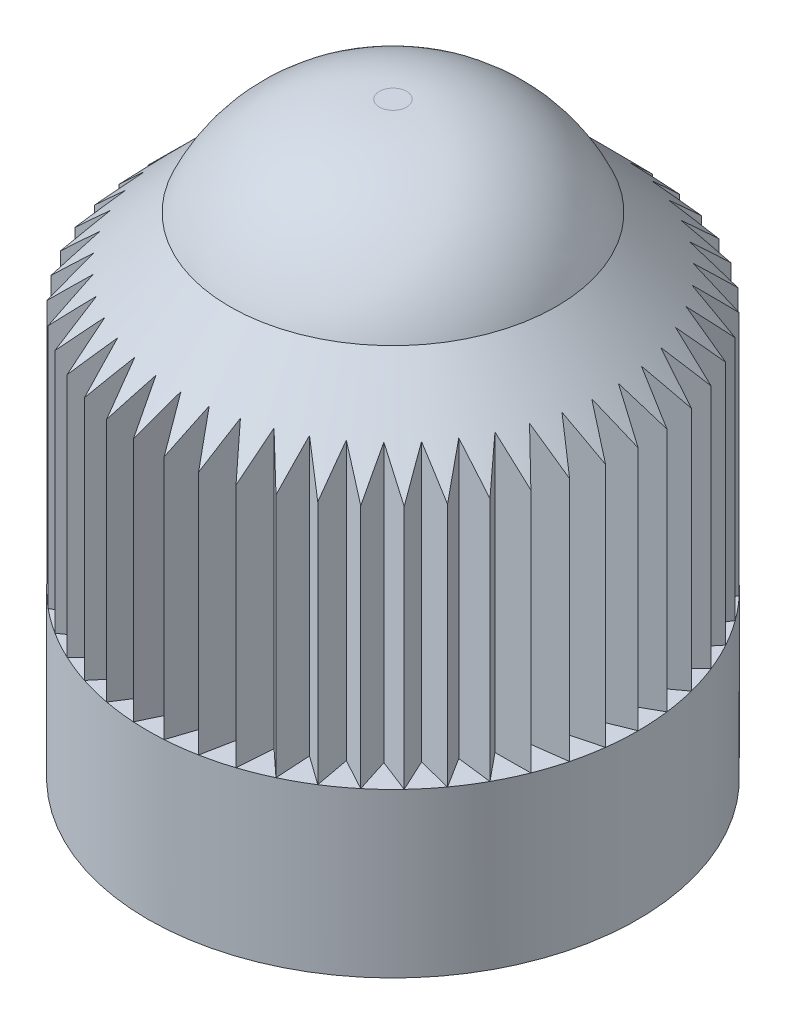
SolidWorks part; units mm, degrees
ref_plane "Спереди" through (0, 0, 0) normal (0, 0, 1) x (1, 0, 0)
ref_plane "Сверху" through (0, 0, 0) normal (0, 1, 0) x (1, 0, 0)
ref_plane "Справа" through (0, 0, 0) normal (1, 0, 0) x (0, 0, -1)
sketch "Sketch1" plane through (0, 0, 0) normal (0, 1, 0) x (1, 0, 0)
  circle A0 centre (0, 0) radius 7.5
  dimension "D1" = 15
extrude "Boss-Extrude1" add sketch "Sketch1" along normal blind 18
sketch "Sketch2" plane through (0, 0, 0) normal (0, -1, 0) x (1, 0, 0)
  circle A0 centre (0, 0) radius 6.5
  dimension "D1" = 13
extrude "Cut-Extrude1" cut sketch "Sketch2" against normal blind 3
sketch "Sketch3" plane through (0, 3, 0) normal (0, -1, 0) x (1, 0, 0)
  line L0 (-1.7426, -2.6839) -> (3.1363, -0.6354)
  line L1 (0.6968, -1.6596) -> (-1.2388, 2.9505) construction
  circle A0 centre (0, 0) radius 3.2 construction
  arc A1 (-1.7426, -2.6839) -> (3.1363, -0.6354) centre (0, 0) cw
  dimension "D1" = 6.4
  dimension "D2" = 5
extrude "Cut-Extrude2" cut sketch "Sketch3" against normal blind 12
chamfer "Chamfer1" distance 1 angle 30 1 edges at (0, 0, -6.5) first distance on face at (0, 3, -6.5)
sketch "Sketch4" plane through (0, 18, 0) normal (0, 1, 0) x (1, 0, 0)
  circle A0 centre (0, 0) radius 5
  dimension "D1" = 10
extrude "Cut-Extrude3" cut sketch "Sketch4" against normal blind 13 flip side to cut
chamfer "Chamfer2" distance 10 angle 45 1 edges at (0, 5, 5)
sketch "Sketch5" plane through (0, 18, 0) normal (0, 1, 0) x (1, 0, 0)
  line L0 (2.3986, -6.0413) -> (2.3244, -7.1307)
  line L1 (2.3244, -7.1307) -> (1.6225, -6.2942)
  line L2 (1.6225, -6.2942) -> (1.4124, -7.3658)
  line L3 (1.4124, -7.3658) -> (0.8208, -6.448)
  line L4 (0.8208, -6.448) -> (0.4781, -7.4847)
  line L5 (0.4781, -7.4847) -> (0.0062, -6.5)
  line L6 (0.0062, -6.5) -> (-0.4638, -7.4856)
  line L7 (-0.4638, -7.4856) -> (-0.8085, -6.4495)
  line L8 (-0.8085, -6.4495) -> (-1.3983, -7.3685)
  line L9 (-1.3983, -7.3685) -> (-1.6105, -6.2973)
  line L10 (-1.6105, -6.2973) -> (-2.3108, -7.1351)
  line L11 (-2.3108, -7.1351) -> (-2.3871, -6.0458)
  line L12 (-2.3871, -6.0458) -> (-3.1869, -6.7892)
  line L13 (-3.1869, -6.7892) -> (-3.126, -5.699)
  line L14 (-3.126, -5.699) -> (-4.0127, -6.3363)
  line L15 (-4.0127, -6.3363) -> (-3.8156, -5.2622)
  line L16 (-3.8156, -5.2622) -> (-4.7752, -5.7834)
  line L17 (-4.7752, -5.7834) -> (-4.445, -4.7425)
  line L18 (-4.445, -4.7425) -> (-5.4624, -5.1393)
  line L19 (-5.4624, -5.1393) -> (-5.0044, -4.148)
  line L20 (-5.0044, -4.148) -> (-6.0634, -4.4142)
  line L21 (-6.0634, -4.4142) -> (-5.4848, -3.4881)
  line L22 (-5.4848, -3.4881) -> (-6.5689, -3.6194)
  line L23 (-6.5689, -3.6194) -> (-5.8787, -2.7732)
  line L24 (-5.8787, -2.7732) -> (-6.9707, -2.7676)
  line L25 (-6.9707, -2.7676) -> (-6.18, -2.0145)
  line L26 (-6.18, -2.0145) -> (-7.2626, -1.8721)
  line L27 (-7.2626, -1.8721) -> (-6.3837, -1.2241)
  line L28 (-6.3837, -1.2241) -> (-7.44, -0.9471)
  line L29 (-7.44, -0.9471) -> (-6.4868, -0.4143)
  line L30 (-6.4868, -0.4143) -> (-7.5, -0.0071)
  line L31 (-7.5, -0.0071) -> (-6.4876, 0.402)
  line L32 (-6.4876, 0.402) -> (-7.4418, 0.9329)
  line L33 (-7.4418, 0.9329) -> (-6.386, 1.2119)
  line L34 (-6.386, 1.2119) -> (-7.2661, 1.8583)
  line L35 (-7.2661, 1.8583) -> (-6.1838, 2.0027)
  line L36 (-6.1838, 2.0027) -> (-6.9759, 2.7543)
  line L37 (-6.9759, 2.7543) -> (-5.884, 2.762)
  line L38 (-5.884, 2.762) -> (-6.5757, 3.6069)
  line L39 (-6.5757, 3.6069) -> (-5.4914, 3.4777)
  line L40 (-5.4914, 3.4777) -> (-6.0718, 4.4026)
  line L41 (-6.0718, 4.4026) -> (-5.0123, 4.1385)
  line L42 (-5.0123, 4.1385) -> (-5.4721, 5.1289)
  line L43 (-5.4721, 5.1289) -> (-4.4541, 4.7341)
  line L44 (-4.4541, 4.7341) -> (-4.7862, 5.7743)
  line L45 (-4.7862, 5.7743) -> (-3.8256, 5.255)
  line L46 (-3.8256, 5.255) -> (-4.0247, 6.3286)
  line L47 (-4.0247, 6.3286) -> (-3.1368, 5.693)
  line L48 (-3.1368, 5.693) -> (-3.1998, 6.7832)
  line L49 (-3.1998, 6.7832) -> (-2.3986, 6.0413)
  line L50 (-2.3986, 6.0413) -> (-2.3244, 7.1307)
  line L51 (-2.3244, 7.1307) -> (-1.6225, 6.2942)
  line L52 (-1.6225, 6.2942) -> (-1.4124, 7.3658)
  line L53 (-1.4124, 7.3658) -> (-0.8208, 6.448)
  line L54 (-0.8208, 6.448) -> (-0.4781, 7.4847)
  line L55 (-0.4781, 7.4847) -> (-0.0062, 6.5)
  line L56 (-0.0062, 6.5) -> (0.4638, 7.4856)
  line L57 (0.4638, 7.4856) -> (0.8085, 6.4495)
  line L58 (0.8085, 6.4495) -> (1.3983, 7.3685)
  line L59 (1.3983, 7.3685) -> (1.6105, 6.2973)
  line L60 (1.6105, 6.2973) -> (2.3108, 7.1351)
  line L61 (2.3108, 7.1351) -> (2.3871, 6.0458)
  line L62 (2.3871, 6.0458) -> (3.1869, 6.7892)
  line L63 (3.1869, 6.7892) -> (3.126, 5.699)
  line L64 (3.126, 5.699) -> (4.0127, 6.3363)
  line L65 (4.0127, 6.3363) -> (3.8156, 5.2622)
  line L66 (3.8156, 5.2622) -> (4.7752, 5.7834)
  line L67 (4.7752, 5.7834) -> (4.445, 4.7425)
  line L68 (4.445, 4.7425) -> (5.4624, 5.1393)
  line L69 (5.4624, 5.1393) -> (5.0044, 4.148)
  line L70 (5.0044, 4.148) -> (6.0634, 4.4142)
  line L71 (6.0634, 4.4142) -> (5.4848, 3.4881)
  line L72 (5.4848, 3.4881) -> (6.5689, 3.6194)
  line L73 (6.5689, 3.6194) -> (5.8787, 2.7732)
  line L74 (5.8787, 2.7732) -> (6.9707, 2.7676)
  line L75 (6.9707, 2.7676) -> (6.18, 2.0145)
  line L76 (6.18, 2.0145) -> (7.2626, 1.8721)
  line L77 (7.2626, 1.8721) -> (6.3837, 1.2241)
  line L78 (6.3837, 1.2241) -> (7.44, 0.9471)
  line L79 (7.44, 0.9471) -> (6.4868, 0.4143)
  line L80 (6.4868, 0.4143) -> (7.5, 0.0071)
  line L81 (7.5, 0.0071) -> (6.4876, -0.402)
  line L82 (6.4876, -0.402) -> (7.4418, -0.9329)
  line L83 (7.4418, -0.9329) -> (6.386, -1.2119)
  line L84 (6.386, -1.2119) -> (7.2661, -1.8583)
  line L85 (7.2661, -1.8583) -> (6.1838, -2.0027)
  line L86 (6.1838, -2.0027) -> (6.9759, -2.7543)
  line L87 (6.9759, -2.7543) -> (5.884, -2.762)
  line L88 (5.884, -2.762) -> (6.5757, -3.6069)
  line L89 (6.5757, -3.6069) -> (5.4914, -3.4777)
  line L90 (5.4914, -3.4777) -> (6.0718, -4.4026)
  line L91 (6.0718, -4.4026) -> (5.0123, -4.1385)
  line L92 (5.0123, -4.1385) -> (5.4721, -5.1289)
  line L93 (5.4721, -5.1289) -> (4.4541, -4.7341)
  line L94 (4.4541, -4.7341) -> (4.7862, -5.7743)
  line L95 (4.7862, -5.7743) -> (3.8256, -5.255)
  line L96 (3.8256, -5.255) -> (4.0247, -6.3286)
  line L97 (4.0247, -6.3286) -> (3.1368, -5.693)
  line L98 (3.1368, -5.693) -> (3.1998, -6.7832)
  line L99 (3.1998, -6.7832) -> (2.3986, -6.0413)
  circle A0 centre (0, 0) radius 6.5 construction
  circle A2 centre (0, 0) radius 7.5 construction
  point P156 (0, 0)
  dimension "D1" = 13
  dimension "D2" = 50
extrude "Cut-Extrude4" cut sketch "Sketch5" against normal blind 13 flip side to cut
fillet "Fillet1" radius 5 1 edges at (0, 18, 5)
